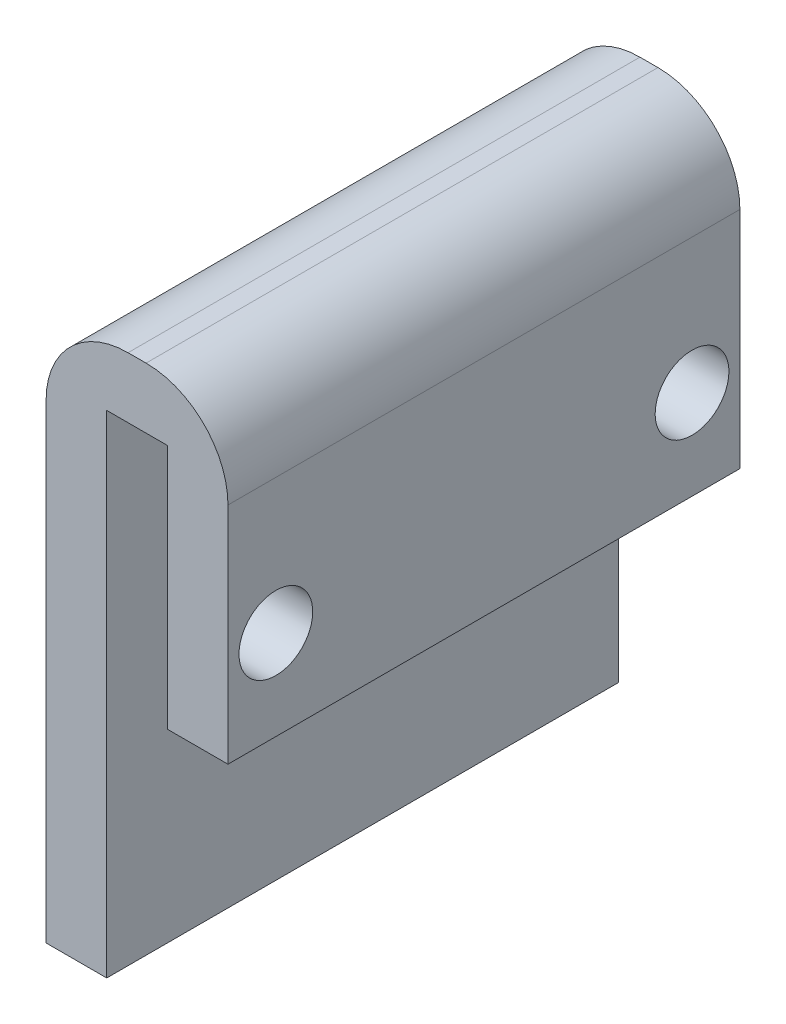
SolidWorks part; units mm, degrees
ref_plane "Front Plane" through (0, 0, 0) normal (0, 0, 1) x (1, 0, 0)
ref_plane "Top Plane" through (0, 0, 0) normal (0, 1, 0) x (1, 0, 0)
ref_plane "Right Plane" through (0, 0, 0) normal (1, 0, 0) x (0, 0, -1)
sketch "Sketch1" plane through (0, 0, 0) normal (0, 0, 1) x (1, 0, 0)
  line L0 (0, 0) -> (0, 30)
  line L1 (0, 30) -> (3.7, 30)
  line L2 (3.7, 30) -> (3.7, 15)
  line L3 (3.7, 15) -> (7.4, 15)
  line L4 (7.4, 15) -> (7.4, 33.7)
  line L5 (7.4, 33.7) -> (-3.7, 33.7)
  line L6 (-3.7, 33.7) -> (-3.7, 0)
  line L7 (-3.7, 0) -> (0, 0)
  point P3 (7.4, 6.3302)
  point P10 (7.4, 16.2308)
  point P11 (7.4, 17.1012)
  dimension "D1" = 3.7
  dimension "D2" = 3.7
  dimension "D3" = 15
  dimension "D4" = 15
extrude "Boss-Extrude1" add sketch "Sketch1" along normal blind 31.242
fillet "Fillet1" radius 5 2 edges at (7.4, 33.7, 15.621) (-3.7, 33.7, 15.621)
sketch "Sketch2" plane through (7.4, 0, 0) normal (1, 0, 0) x (0, 0, -1)
  line L0 (-15.621, 7.6544) -> (-15.621, 14.0158) construction
  line L1 (0, 28.7) -> (-31.242, 28.7) construction
  line L3 (-31.242, 30) -> (0, 30) construction
  line L4 (-31.242, 30) -> (0, 30)
  circle A0 centre (-28.321, 20.475) radius 2.25
  circle A1 centre (-2.921, 20.475) radius 2.25
  point P8 (-15.621, 28.7)
  point P9 (0, 0)
  dimension "D1" = 4.5
  dimension "D2" = 25.4
  dimension "D3" = 9.525
extrude "Cut-Extrude1" cut sketch "Sketch2" against normal up to next contours A0 | A1 region at (7.4, 20.475, 28.321) region at (7.4, 20.475, 2.921)
